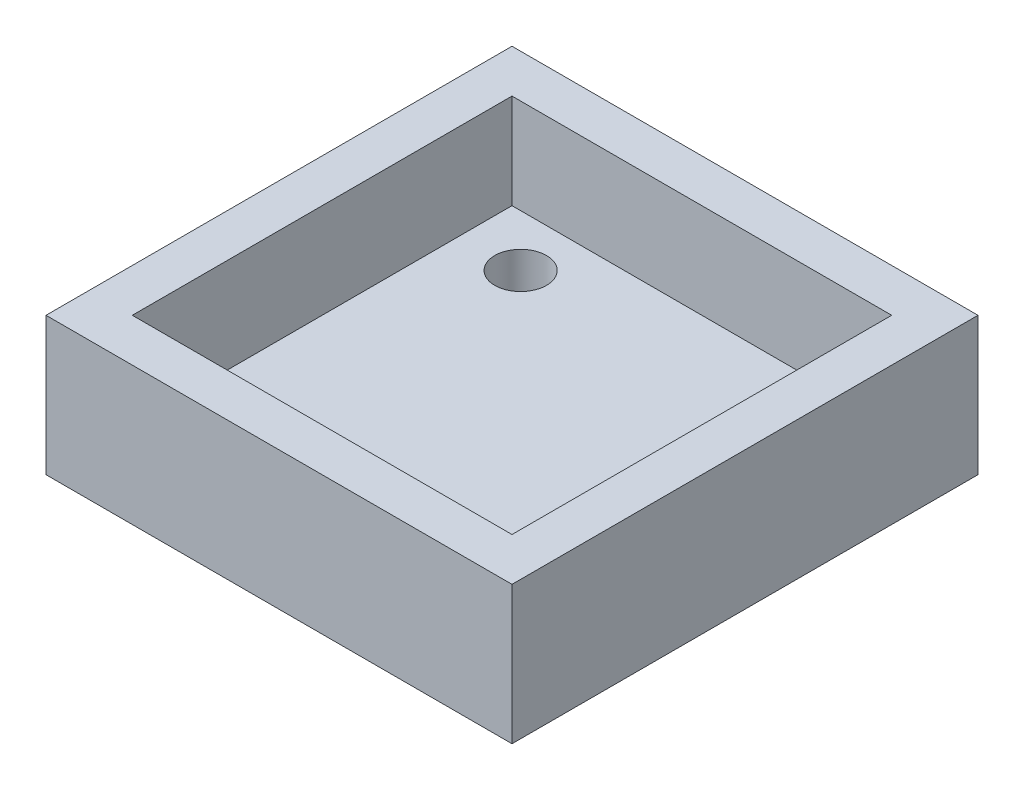
SolidWorks part; units mm, degrees
ref_plane "Front Plane" through (0, 0, 0) normal (0, 0, 1) x (1, 0, 0)
ref_plane "Top Plane" through (0, 0, 0) normal (0, 1, 0) x (1, 0, 0)
ref_plane "Right Plane" through (0, 0, 0) normal (1, 0, 0) x (0, 0, -1)
sketch "Sketch2" plane through (0, 0, 0) normal (0, 1, 0) x (1, 0, 0)
  line L1 (0, 0) -> (27, 0)
  line L2 (0, 0) -> (0, 27)
  line L3 (0, 27) -> (27, 27)
  line L4 (27, 0) -> (27, 27)
  dimension "D1" = 27
  dimension "D2" = 27
extrude "Boss-Extrude1" add sketch "Sketch2" along normal blind 8 contours L2 L1 L4 L3
sketch "Sketch5" plane through (0, 8, 0) normal (0, 1, 0) x (1, 0, 0)
  line L0 (0, 0) -> (27, 0) construction
  line L1 (27, 0) -> (27, 27) construction
  line L5 (2.5, 24.5) -> (24.5, 24.5)
  line L6 (2.5, 24.5) -> (2.5, 2.5)
  line L7 (2.5, 2.5) -> (24.5, 2.5)
  line L8 (24.5, 24.5) -> (24.5, 2.5)
  line L9 (2.5, 24.5) -> (24.5, 2.5) construction
  line L10 (2.5, 2.5) -> (24.5, 24.5) construction
  point P0 (13.5, 13.5)
  dimension "D1" = 22
  dimension "D2" = 22
  dimension "D3" = 2.5
  dimension "D4" = 2.5
extrude "Cut-Extrude2" cut sketch "Sketch5" against normal blind 5.5
sketch "Sketch3" plane through (0, 0, 0) normal (0, -1, 0) x (-1, 0, 0)
  line L3 (0, 27) -> (-27, 27) construction
  circle A1 centre (-6, 21.5) radius 1.5
  circle A2 centre (-6, 5.5) radius 1.5
  dimension "D1" = 3
  dimension "D2" = 3
  dimension "D5" = 16
  dimension "D7" = 6
  dimension "D8" = 5.5
extrude "Cut-Extrude3" cut sketch "Sketch3" against normal blind 10
sketch "Sketch6" plane through (0, 2.5, 0) normal (0, 1, 0) x (1, 0, 0)
  line L0 (0, 27) -> (27, 27) construction
  line L2 (19.5, 21.25) -> (19.5, 5.75)
  line L4 (24.5, 2.5) -> (24.5, 24.5)
  line L5 (24.5, 24.5) -> (2.5, 24.5)
  line L6 (2.5, 24.5) -> (2.5, 2.5)
  line L7 (2.5, 2.5) -> (24.5, 2.5)
  line L8 (24.5, 5.75) -> (24.5, 21.25)
  line L12 (24.5, 21.25) -> (24.5, 5.75)
  line L13 (0, 0) -> (27, 0) construction
  arc A0 (22.25, 3) -> (24.5, 5.75) centre (21.6944, 5.75) ccw
  arc A1 (24.5, 21.25) -> (22.25, 24) centre (21.6944, 21.25) ccw
  arc A2 (19.5, 5.75) -> (22.25, 3) centre (22.25, 5.75) ccw
  arc A3 (22.25, 24) -> (19.5, 21.25) centre (22.25, 21.25) ccw
  line M7 (24.5, 2.5) -> (24.5, 24.5)
  dimension "D2" = 0
  dimension "D3" = 3
  dimension "D4" = 3
  dimension "D1" = 0
extrude "Cut-Extrude4" cut sketch "Sketch6" against normal blind 10 contours A1 A3 L2 A2 A0 M7 region at (22.0014, 2.5, -13.5)
